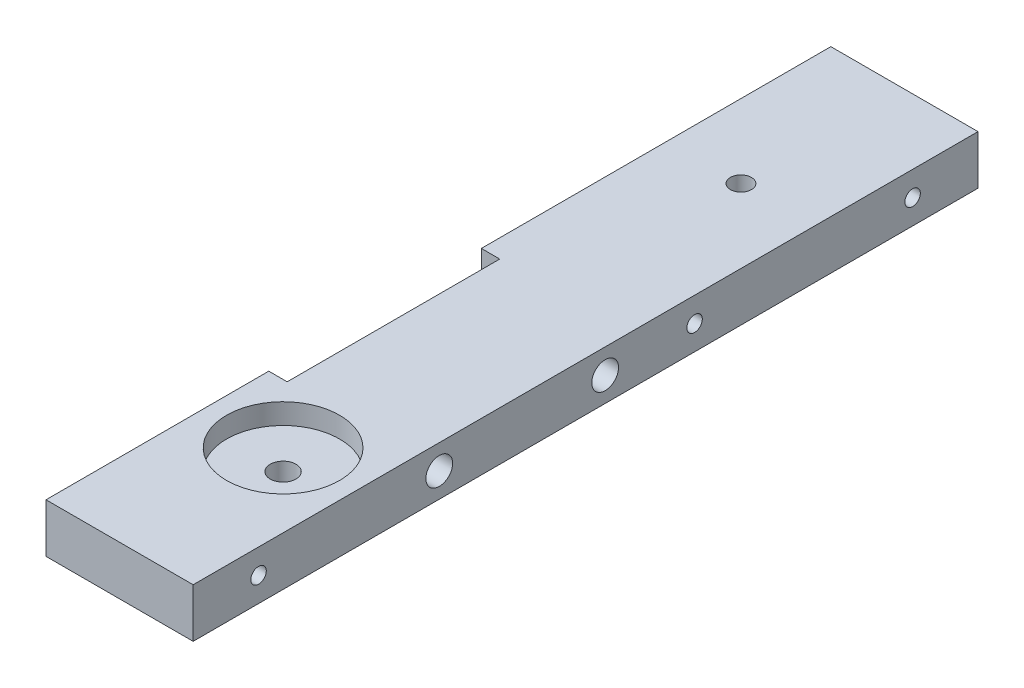
SolidWorks part; units mm, degrees
material "TPU"
ref_plane "Front Plane" through (0, 0, 0) normal (0, 0, 1) x (1, 0, 0)
ref_plane "Top Plane" through (0, 0, 0) normal (0, 1, 0) x (1, 0, 0)
ref_plane "Right Plane" through (0, 0, 0) normal (1, 0, 0) x (0, 0, -1)
sketch "Sketch2" plane through (0, 0, 0) normal (0, 1, 0) x (1, 0, 0)
  line L0 (0, 0) -> (0, 152.4)
  line L1 (0, 152.4) -> (28.575, 152.4)
  line L2 (28.575, 152.4) -> (28.575, 0)
  line L3 (28.575, 0) -> (0, 0)
  dimension "D1" = 152.4
  dimension "D2" = 28.575
extrude "Boss-Extrude1" add sketch "Sketch2" along normal blind 9.525
sketch "Sketch3" plane through (0, 0, 0) normal (-1, 0, 0) x (0, 0, 1)
  line L3 (-152.4, 9.525) -> (0, 9.525) construction
  line L4 (-152.4, 9.525) -> (-152.4, 0) construction
  point P6 (-139.7, 4.7625)
  point P14 (-139.7, 4.7625)
  dimension "D1" = 4.7625
  dimension "D2" = 12.7
sketch "Sketch8" plane through (0, 0, 0) normal (-1, 0, 0) x (0, 0, 1)
  point P0 (-139.7, 4.7625)
hole_wizard "Ø3.0mm Dowel Hole1" positions "Sketch8" profile "Sketch9" hole size "Ø3.0" standard "ANSI Metric" end condition through all
sketch "Sketch9" plane through (0, 4.7625, -139.7) normal (0, 1, 0) x (0, 0, 1)
  line L0 (0, 0) -> (0, 28.575)
  line L1 (0, 28.575) -> (1.5, 28.575)
  line L2 (1.5, 28.575) -> (1.5, 0)
  line L5 (1.5, 0) -> (0, 0)
  line L11 (0, -6.35) -> (0, 107.95) construction
  dimension "Thru Hole Dia." = 3
  dimension "Thru Hole Depth" = 28.575
pattern_linear "LPattern1" count 4 spacing 42.3333 along (0, 0, 1) skipping (2, 0) of "Ø3.0mm Dowel Hole1"
sketch "Sketch12" plane through (0, 9.525, 0) normal (0, 1, 0) x (1, 0, 0)
  line L0 (28.575, 0) -> (28.575, 152.4) construction
  line L2 (0, 0) -> (28.575, 0) construction
  circle A1 centre (14.2875, 31.75) radius 10.975
  circle A2 centre (14.2875, 120.65) radius 2.05
  point P0 (14.2875, 120.65)
  point P1 (14.2875, 76.2)
  point P2 (14.2875, 31.75)
  dimension "D8" = 4.1
  dimension "D9" = 21.95
  dimension "D1" = 14.2875
  dimension "D2" = 14.2875
  dimension "D3" = 14.2875
  dimension "D4" = 76.2
  dimension "D5" = 44.45
  dimension "D6" = 44.45
sketch "Sketch13" plane through (0, 0, 0) normal (-1, 0, 0) x (0, 0, 1)
  line L2 (0, 9.525) -> (0, 0) construction
  line L3 (-152.4, 9.525) -> (0, 9.525) construction
  circle A0 centre (-80, 4.7625) radius 2.6
  circle A1 centre (-47.79, 4.7625) radius 2.6
  point P5 (-80, 4.7625)
  point P11 (-47.79, 4.7625)
  dimension "D1" = 80
  dimension "D2" = 4.7625
  dimension "D3" = 32.21
extrude "Cut-Extrude1" cut sketch "Sketch12" against normal through all contours A2
extrude "Cut-Extrude2" cut sketch "Sketch12<4>" against normal blind 4 contours A1
sketch "Sketch12<4>" plane through (0, 9.525, 0) normal (0, 1, 0) x (1, 0, 0) same geometry as "Sketch12"
sketch "Sketch15" plane through (0, 5.525, 0) normal (0, 1, 0) x (1, 0, 0)
  circle A0 centre (14.2875, 31.75) radius 2.5
  dimension "D1" = 5
extrude "Cut-Extrude3" cut sketch "Sketch15" against normal through all
extrude "Cut-Extrude4" cut sketch "Sketch13" against normal through all
sketch "Sketch17" plane through (0, 0, 0) normal (-1, 0, 0) x (0, 0, 1)
  line L0 (-152.4, 9.525) -> (0, 9.525) construction
  line L1 (-84.535, 9.525) -> (-43.255, 9.525)
  line L2 (-84.535, 9.525) -> (-84.535, 0)
  line L3 (-84.535, 0) -> (-43.255, 0)
  line L4 (-43.255, 9.525) -> (-43.255, 0)
  line L5 (-152.4, 0) -> (0, 0) construction
  circle A3 centre (-80, 4.7625) radius 2.6 construction
  circle A4 centre (-47.79, 4.7625) radius 2.6 construction
  point P12 (-84.535, 4.7625)
  dimension "D2" = 41.28
  dimension "D1" = 32.21
  dimension "D4" = 4.535
  dimension "D3" = 4.535
extrude "Cut-Extrude5" cut sketch "Sketch17" against normal offset from surface (3.575 mm away) 25 up to face at (28.575, 4.7625, -77.4)
